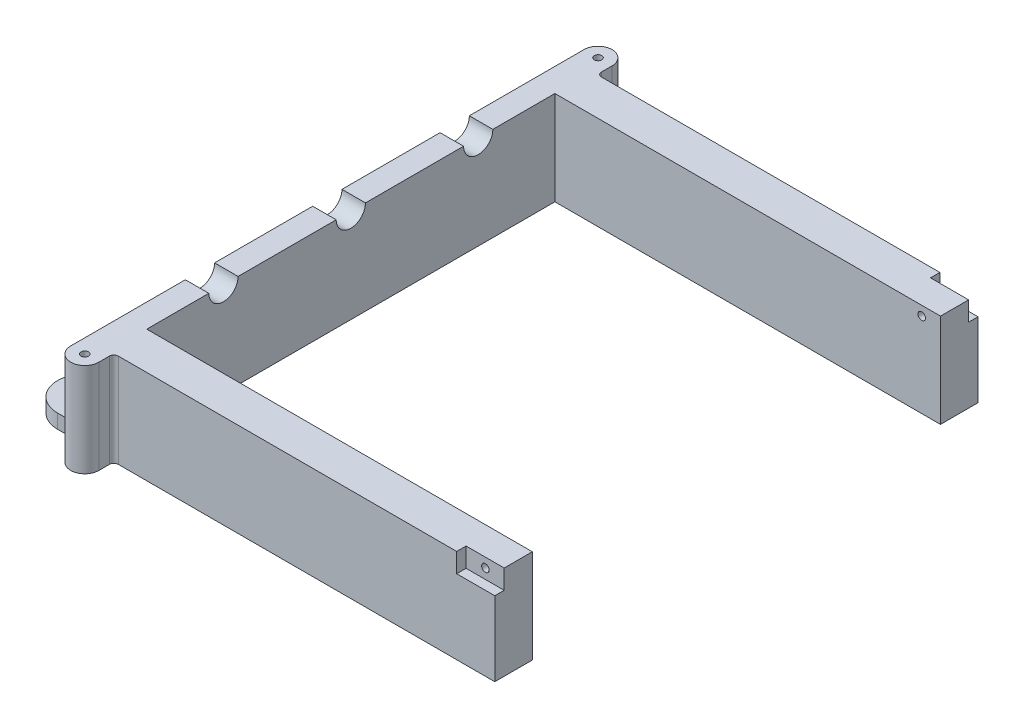
SolidWorks part; units mm, degrees
ref_plane "Front Plane" through (0, 0, 0) normal (0, 0, 1) x (1, 0, 0)
ref_plane "Top Plane" through (0, 0, 0) normal (0, 1, 0) x (1, 0, 0)
ref_plane "Right Plane" through (0, 0, 0) normal (1, 0, 0) x (0, 0, -1)
sketch "Sketch1" plane through (0, 0, 0) normal (0, 1, 0) x (1, 0, 0)
  line L0 (-138.43, 81.7626) -> (138.43, 81.7626)
  line L1 (-130.4798, -69.0626) -> (130.4798, -69.0626)
  line L2 (-130.4798, -69.0626) -> (-130.4798, 69.0626)
  line L3 (-130.4798, 69.0626) -> (130.4798, 69.0626)
  line L4 (130.4798, -69.0626) -> (130.4798, 69.0626)
  line L5 (-130.4798, -69.0626) -> (130.4798, 69.0626) construction
  line L6 (-130.4798, 69.0626) -> (130.4798, -69.0626) construction
  line L7 (138.43, -81.7626) -> (138.43, 81.7626)
  line L8 (-138.43, -81.7626) -> (138.43, -81.7626)
  line L9 (-138.43, -81.7626) -> (-138.43, 81.7626)
  point P0 (0, 0)
  dimension "D1" = 138.1252
  dimension "D2" = 260.9596
  dimension "D3" = 12.7
  dimension "D4" = 12.7
  dimension "D5" = 7.9502
  dimension "D6" = 7.9502
extrude "Boss-Extrude1" add sketch "Sketch1" along normal blind 31.75
sketch "Sketch2" plane through (138.43, 0, 0) normal (1, 0, 0) x (0, 0, -1)
  line L0 (-81.7626, 31.75) -> (81.7626, 31.75) construction
  circle A0 centre (0, 31.75) radius 4.953
  circle A1 centre (43.1038, 31.75) radius 4.953
  circle A2 centre (-43.1038, 31.75) radius 4.953
  dimension "D1" = 9.906
  dimension "D2" = 43.1038
  dimension "D3" = 43.1038
extrude "Cut-Extrude1" cut sketch "Sketch2" against normal through all
sketch "Sketch3" plane through (0, 31.75, 0) normal (0, 1, 0) x (1, 0, 0)
  line L0 (-138.43, 81.7626) -> (-138.43, 86.8426)
  line L1 (-128.905, 81.7626) -> (-128.905, 86.8426)
  line L2 (138.43, 81.7626) -> (-138.43, 81.7626) construction
  line L3 (-138.43, 81.7626) -> (-128.905, 81.7626)
  arc A0 (-138.43, 86.8426) -> (-128.905, 86.8426) centre (-133.6675, 86.8426) cw
  circle A1 centre (-133.6675, 86.8426) radius 1.27
  dimension "D3" = 2.54
  dimension "D1" = 5.08
  dimension "D2" = 9.525
extrude "Boss-Extrude2" add sketch "Sketch3" against normal through all
mirror "Mirror3" about plane through (0, 0, 0) normal (1, 0, 0) of "Boss-Extrude2"
mirror "Mirror4" about plane through (0, 0, 0) normal (0, 0, 1) of "Boss-Extrude2", "Mirror3"
fillet "Fillet2" radius 1.524 4 edges at (-128.905, 15.875, 81.7626) (128.905, 15.875, 81.7626) (128.905, 15.875, -81.7626) (-128.905, 15.875, -81.7626)
sketch "Sketch4" plane through (0, 0, -81.7626) normal (0, 0, -1) x (-1, 0, 0)
  line L0 (-127.381, 31.75) -> (127.381, 31.75) construction
  line L1 (-12.8905, 25.2095) -> (12.8905, 25.2095)
  line L2 (-12.8905, 25.2095) -> (-12.8905, 38.2905)
  line L3 (-12.8905, 38.2905) -> (12.8905, 38.2905)
  line L4 (12.8905, 25.2095) -> (12.8905, 38.2905)
  line L5 (-12.8905, 25.2095) -> (12.8905, 38.2905) construction
  line L6 (-12.8905, 38.2905) -> (12.8905, 25.2095) construction
  point P0 (0, 31.75)
  dimension "D1" = 13.081
  dimension "D2" = 25.781
extrude "Cut-Extrude2" cut sketch "Sketch4" against normal blind 3.175
sketch "Sketch5" plane through (0, 0, -78.5876) normal (0, 0, -1) x (-1, 0, 0)
  line L0 (-12.8905, 31.75) -> (12.8905, 31.75) construction
  circle A0 centre (-6.35, 28.575) radius 1.27
  circle A1 centre (6.35, 28.575) radius 1.27
  dimension "D3" = 2.54
  dimension "D4" = 2.54
  dimension "D1" = 3.175
  dimension "D2" = 6.35
  dimension "D5" = 6.35
  dimension "D6" = 3.175
extrude "Cut-Extrude3" cut sketch "Sketch5" against normal up to next
mirror "Mirror5" about plane through (0, 0, 0) normal (0, 0, 1) of "Cut-Extrude2", "Cut-Extrude3"
sketch "Sketch6" plane through (0, 31.75, 0) normal (0, 1, 0) x (1, 0, 0)
  line L0 (0, 0) -> (0, 94.7828)
  line L1 (0, 94.7828) -> (154.5003, 94.7828)
  line L2 (154.5003, 94.7828) -> (154.5003, -104.417)
  line L3 (0, 0) -> (0, -98.8915)
  line L4 (0, -98.8915) -> (154.5003, -104.417)
extrude "Cut-Extrude4" cut sketch "Sketch6" against normal through all
sketch "Sketch7" plane through (0, 0, 0) normal (0, -1, 0) x (1, 0, 0)
  line L0 (-138.43, 81.7626) -> (-147.955, 81.7626)
  line L1 (-138.43, -86.8426) -> (-138.43, 86.8426) construction
  line L2 (-127.381, 81.7626) -> (0, 81.7626) construction
  line L3 (-138.43, 62.7126) -> (-147.955, 62.7126)
  line L4 (-138.43, 81.7626) -> (-138.43, 62.7126)
  arc A0 (-147.955, 81.7626) -> (-147.955, 62.7126) centre (-147.955, 72.2376) ccw
  circle A1 centre (-147.955, 72.2376) radius 3.556
  dimension "D3" = 7.112
  dimension "D1" = 19.05
  dimension "D2" = 9.525
extrude "Boss-Extrude3" add sketch "Sketch7" against normal blind 4.7752
mirror "Mirror6" about plane through (0, 0, 0) normal (0, 0, 1) of "Boss-Extrude3"
fillet "Fillet3" radius 9.525 2 edges at (-138.43, 2.3876, -62.7126) (-138.43, 2.3876, 62.7126)
